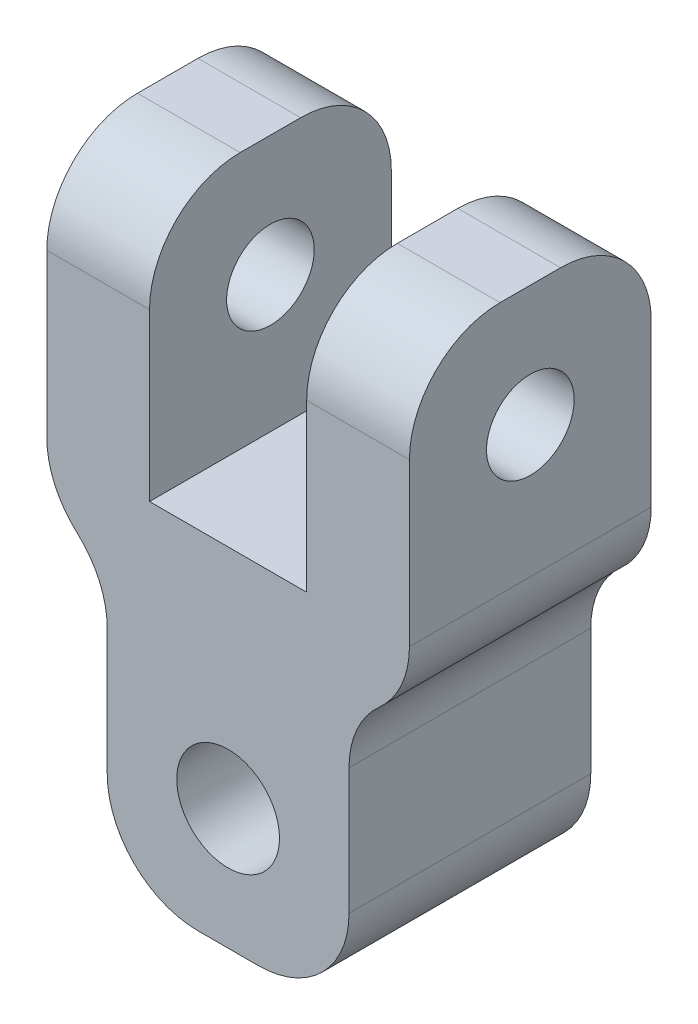
SolidWorks part; units mm, degrees
ref_plane "Front" through (0, 0, 0) normal (0, 0, 1) x (1, 0, 0)
ref_plane "Top" through (0, 0, 0) normal (0, 1, 0) x (1, 0, 0)
ref_plane "Right" through (0, 0, 0) normal (1, 0, 0) x (0, 0, -1)
sketch "草图1" plane through (0, 0, 0) normal (0, 1, 0) x (1, 0, 0)
  line L1 (0, 0) -> (8, 0)
  line L2 (0, 0) -> (0, -8)
  line L3 (0, -8) -> (8, -8)
  line L4 (8, 0) -> (8, -8)
  dimension "D1" = 8
  dimension "D2" = 8
extrude "凸台-拉伸1" add sketch "草图1" along normal blind 20
sketch "草图2" plane through (0, 0, 8) normal (0, 0, 1) x (1, 0, 0)
  line L0 (0, 0) -> (8, 0) construction
  line L1 (8, 20) -> (8, 0) construction
  circle A0 centre (4, 4) radius 1.7
  dimension "D1" = 3.4
  dimension "D2" = 4
  dimension "D3" = 4
extrude "切除-拉伸1" cut sketch "草图2" against normal through all
sketch "草图4" plane through (0, 20, 0) normal (0, 1, 0) x (1, 0, 0)
  line L1 (0, 0) -> (-2, 0)
  line L2 (0, 0) -> (0, -8)
  line L3 (0, -8) -> (-2, -8)
  line L4 (-2, 0) -> (-2, -8)
  line L5 (8, 0) -> (10, 0)
  line L6 (8, 0) -> (8, -8)
  line L7 (8, -8) -> (10, -8)
  line L8 (10, 0) -> (10, -8)
  dimension "D1" = 2
  dimension "D2" = 2
  dimension "D3" = 8
  dimension "D4" = 8
extrude "凸台-拉伸3" add sketch "草图4" against normal blind 10
sketch "草图5" plane through (0, 0, 8) normal (0, 0, 1) x (1, 0, 0)
  line L0 (-2, 20) -> (10, 20) construction
  line L1 (1.4, 20) -> (6.6, 20)
  line L2 (1.4, 20) -> (1.4, 11.5)
  line L3 (1.4, 11.5) -> (6.6, 11.5)
  line L4 (6.6, 20) -> (6.6, 11.5)
  dimension "D1" = 5.2
  dimension "D2" = 3.4
  dimension "D3" = 8.5
extrude "切除-拉伸2" cut sketch "草图5" against normal through all
fillet "圆角1" radius 3 2 edges at (8, 10, 4) (0, 10, 4)
sketch "草图6" plane through (10, 0, 0) normal (1, 0, 0) x (0, 0, -1)
  line L0 (-8, 20) -> (0, 20) construction
  line L1 (0, 10) -> (0, 20) construction
  circle A0 centre (-4, 16) radius 1.45
  dimension "D1" = 2.9
  dimension "D2" = 4
  dimension "D3" = 4
extrude "切除-拉伸3" cut sketch "草图6" against normal through all
fillet "圆角2" radius 3 6 edges at (-2, 10, 4) (10, 10, 4) (-0.3, 20, 0) (-0.3, 20, 8) (0, 0, 4) (8, 0, 4)
